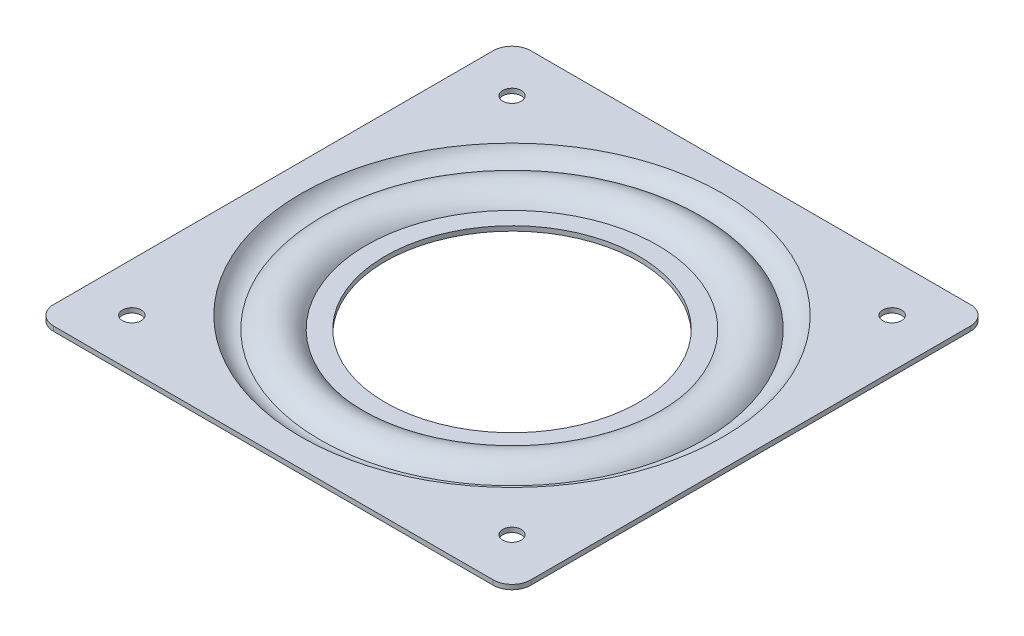
SolidWorks part; units mm, degrees
ref_plane "前视基准面" through (0, 0, 0) normal (0, 0, 1) x (1, 0, 0)
ref_plane "上视基准面" through (0, 0, 0) normal (0, 1, 0) x (1, 0, 0)
ref_plane "右视基准面" through (0, 0, 0) normal (1, 0, 0) x (0, 0, -1)
sketch "草图1" plane through (0, 0, 0) normal (0, 0, 1) x (1, 0, 0)
  line L0 (-36.7805, 0) -> (-35.9228, 0)
  line L1 (0, 6.9172) -> (0, -6.9172) construction
  line L2 (-31, -2.5698) -> (-27, -2.5698)
  line L3 (-35.9228, 0) -> (0, 0) construction
  line L4 (0, 0) -> (43.3864, 0) construction
  line L5 (-43.3864, 0) -> (-36.7805, 0) construction
  line L6 (-31.5531, -3.5698) -> (-27, -3.5698)
  line L7 (-27, -2.5698) -> (-27, -3.5698)
  line L8 (-44.9105, 0) -> (-45.8139, -0.4289)
  arc A0 (-44.9105, 0) -> (-40.8455, -2.5698) centre (-40.8455, 1.9302) ccw
  arc A1 (-40.8455, -2.5698) -> (-31, -2.5698) centre (-35.9228, -6) cw
  arc A2 (-40.8455, -2.5698) -> (-36.8127, -0.0664) centre (-40.8455, 1.9302) ccw construction
  arc A3 (-36.8127, -0.0664) -> (-36.7805, 0) centre (-40.8455, 1.9302) ccw
  arc A4 (-45.8139, -0.4289) -> (-40.2759, -3.5402) centre (-40.8455, 1.9302) ccw
  arc A5 (-40.2759, -3.5402) -> (-31.5531, -3.5698) centre (-35.9228, -6) cw
  point P4 (0, 0)
  point P8 (0, 0)
  dimension "D1" = 4.5
  dimension "D2" = 6
  dimension "D3" = 27
  dimension "D4" = 4
revolve "旋转1" add sketch "草图1" angle 360 about L1 region at (-33.2348, -0.8509, 0)
sketch "草图2" plane through (0, 0, 0) normal (0, 1, 0) x (1, 0, 0)
  line L1 (-46.8, 50.8) -> (46.8, 50.8)
  line L2 (-50.8, 46.8) -> (-50.8, -46.8)
  line L3 (-46.8, -50.8) -> (46.8, -50.8)
  line L4 (50.8, 46.8) -> (50.8, -46.8)
  line L5 (-50.8, 50.8) -> (50.8, -50.8) construction
  line L6 (-50.8, -50.8) -> (50.8, 50.8) construction
  circle A0 centre (0, 0) radius 44.9105 construction
  circle A1 centre (0, 0) radius 44.9105
  arc A2 (-46.8, 50.8) -> (-50.8, 46.8) centre (-46.8, 46.8) ccw
  circle A3 centre (-40.48, 40.48) radius 1.985
  circle A4 centre (40.48, 40.48) radius 1.985
  arc A5 (50.8, 46.8) -> (46.8, 50.8) centre (46.8, 46.8) ccw
  circle A6 centre (40.48, -40.48) radius 1.985
  arc A7 (46.8, -50.8) -> (50.8, -46.8) centre (46.8, -46.8) ccw
  circle A8 centre (-40.48, -40.48) radius 1.985
  arc A9 (-50.8, -46.8) -> (-46.8, -50.8) centre (-46.8, -46.8) ccw
  point P14 (0, 0)
  point P32 (0, 0)
  dimension "D3" = 4
  dimension "D4" = 3.97
  dimension "D5" = 4
  dimension "D1" = 90
  dimension "D2" = 101.6
  dimension "D6" = 57.2474
extrude "凸台-拉伸1" add sketch "草图2" against normal blind 1 contours L2 L3 L4 L1 A2 A3 A1 region at (0, 0, -49.3632)
